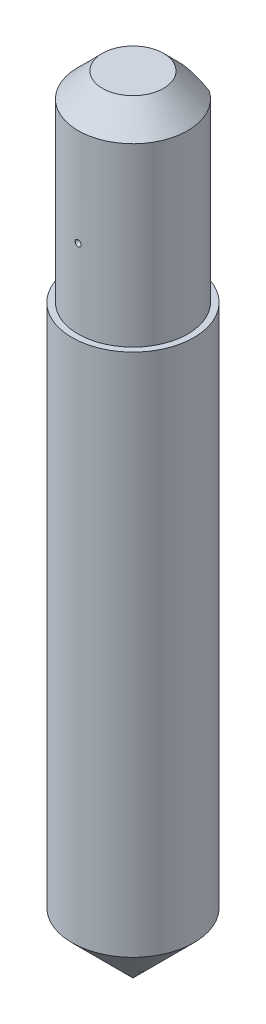
SolidWorks part; units mm, degrees
ref_plane "Front Plane" through (0, 0, 0) normal (0, 0, 1) x (1, 0, 0)
ref_plane "Top Plane" through (0, 0, 0) normal (0, 1, 0) x (1, 0, 0)
ref_plane "Right Plane" through (0, 0, 0) normal (1, 0, 0) x (0, 0, -1)
sketch "Sketch1" plane through (0, 0, 0) normal (0, 1, 0) x (1, 0, 0)
  circle A0 centre (0, 0) radius 5
  dimension "D1" = 10
extrude "Boss-Extrude1" add sketch "Sketch1" along normal blind 48
chamfer "Chamfer1" distance 5 angle 45 1 edges at (0, 0, 5)
sketch "Sketch2" plane through (0, 48, 0) normal (0, 1, 0) x (1, 0, 0)
  line L1 (-2.5612, 3.7) -> (2.5612, 3.7)
  arc A0 (-2.5612, 3.7) -> (2.5612, 3.7) centre (0, 0) ccw
  point P5 (0, -4.5)
  dimension "D1" = 9
  dimension "D2" = 8.2
extrude "Boss-Extrude2" add sketch "Sketch2" along normal blind 16.45
chamfer "Chamfer2" distance 2 angle 45 1 edges at (0, 64.45, 4.5)
sketch "Sketch3" plane through (0, 0, 0) normal (1, 0, 0) x (0, 0, -1)
  line L0 (-4.5, 54.2) -> (-4.5, 54.7)
  line L1 (2.5, 64.45) -> (-2.5, 64.45) construction
  line L2 (-4.5, 48) -> (-4.5, 62.45) construction
  line L3 (0, 64.45) -> (0, 0) construction
  arc A0 (-4.5, 54.7) -> (-4.5, 54.2) centre (-4.5, 54.45) cw
  dimension "D1" = 10
  dimension "D2" = 0.5
revolve "Cut-Revolve1" cut sketch "Sketch3" angle 360 about L0
pattern_circular "CirPattern1" [suppressed] count 3 over 360 about axis through (0, 64.45, 0) along (0, -1, 0) of bodies 103
